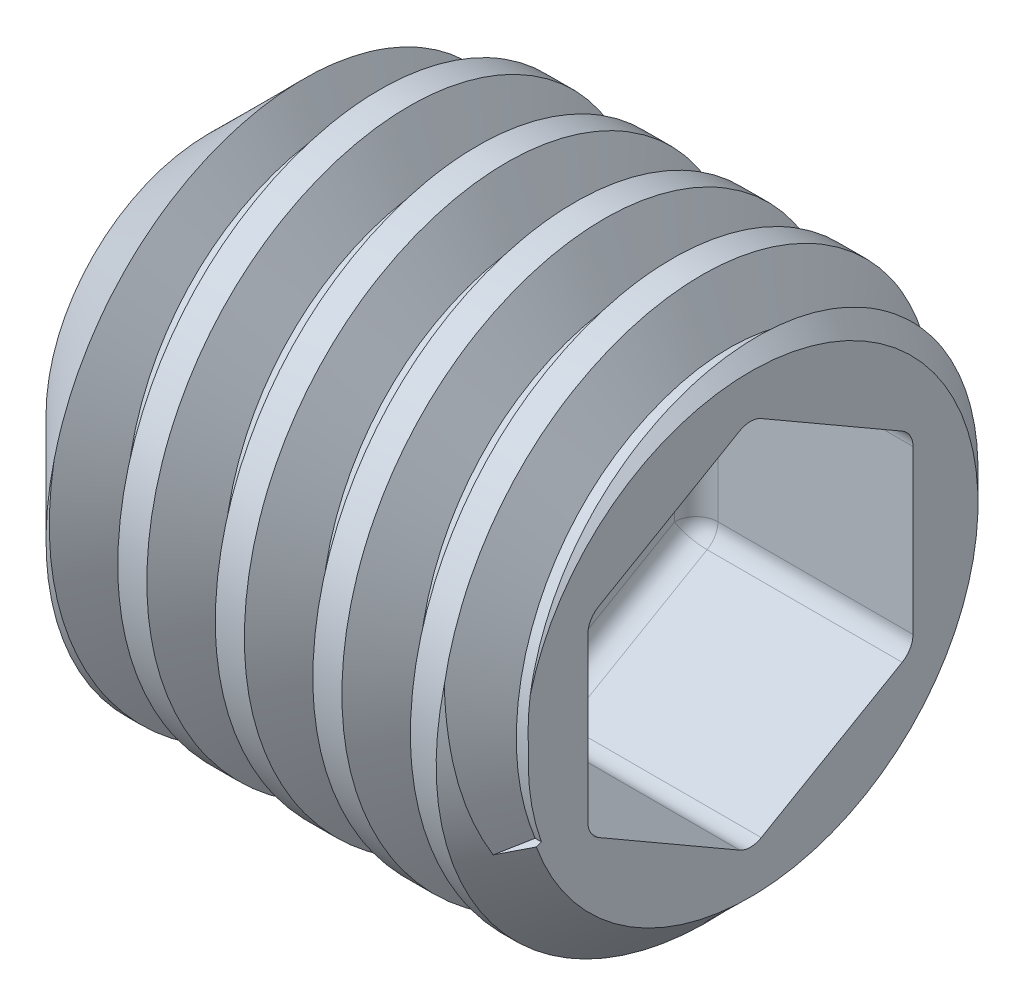
SolidWorks part; units mm, degrees
ref_plane "Plano frontal" through (0, 0, 0) normal (0, 0, 1) x (1, 0, 0)
ref_plane "Plano superior" through (0, 0, 0) normal (0, 1, 0) x (1, 0, 0)
ref_plane "Plano direito" through (0, 0, 0) normal (1, 0, 0) x (0, 0, -1)
sketch "Esboço1" plane through (0, 0, 0) normal (0, 0, 1) x (1, 0, 0)
  line L0 (0, 0) -> (-2.4252, 0) construction
  line L1 (0, 0) -> (2.5, 0)
  line L2 (2.5, 0) -> (2.5, 1.05)
  line L3 (2.3, 1.25) -> (0.5, 1.25)
  line L4 (0, 0.75) -> (0, 0)
  line L5 (2.5, 1.05) -> (2.3, 1.25)
  line L6 (0.5, 1.25) -> (0, 0.75)
  point P3 (0, 1.25)
  point P5 (2.5, 1.25)
  dimension "D1" = 2.5
  dimension "D2" = 2.5
revolve "Revolução1" add sketch "Esboço1" angle 360 about L0
sketch "Esboço2" plane through (2.5, 0, 0) normal (1, 0, 0) x (0, 0, -1)
  line L1 (0, 0.866) -> (-0.75, 0.433)
  line L2 (-0.75, 0.433) -> (-0.75, -0.433)
  line L3 (-0.75, -0.433) -> (0, -0.866)
  line L4 (0, -0.866) -> (0.75, -0.433)
  line L5 (0.75, -0.433) -> (0.75, 0.433)
  line L6 (0.75, 0.433) -> (0, 0.866)
  circle A0 centre (0, 0) radius 0.75 construction
  dimension "D1" = 1.5
extrude "Corte-extrusão1" cut sketch "Esboço2" against normal blind 1
fillet "Filete1" radius 0.1 12 edges at (1.5, 0, -0.75) (1.5, -0.6495, -0.375) (1.5, -0.6495, 0.375) (1.5, 0, 0.75) (1.5, 0.6495, 0.375) (1.5, 0.6495, -0.375) (2, 0.433, -0.75) (2, -0.433, -0.75) (2, 0.866, 0) (2, 0.433, 0.75) (2, -0.433, 0.75) (2, -0.866, 0)
sketch "Esboço3" plane through (0, 0, 0) normal (-1, 0, 0) x (0, 0, 1)
  circle A0 centre (0, 0) radius 1.025
  dimension "D1" = 2.05
curve "Hélice/Espiral1" pitch 0.45 height 2.5 turns 5.5556
sketch "Esboço4" plane through (0, 0, 0) normal (0, 1, 0) x (1, 0, 0)
  line L0 (0, 1.2859) -> (0, 1.025) construction
  line L1 (0.0281, 1.025) -> (-0.0281, 1.025)
  line L2 (-0.0281, 1.025) -> (-0.158, 1.25)
  line L3 (-0.158, 1.25) -> (-0.2143, 1.25)
  line L4 (-0.2143, 1.25) -> (-0.2143, 1.2859)
  line L5 (-0.2143, 1.2859) -> (0.2143, 1.2859)
  line L6 (0.0281, 1.025) -> (0.158, 1.25)
  line L7 (0.158, 1.25) -> (0.2143, 1.25)
  line L8 (0.2143, 1.25) -> (0.2143, 1.2859)
  line L9 (2.3, 1.25) -> (0.5, 1.25) construction
  dimension "D1" = 0.0563
  dimension "D2" = 60
sweep "Varredura de corte1" cut profiles "Esboço4" path "Hélice/Espiral1"
